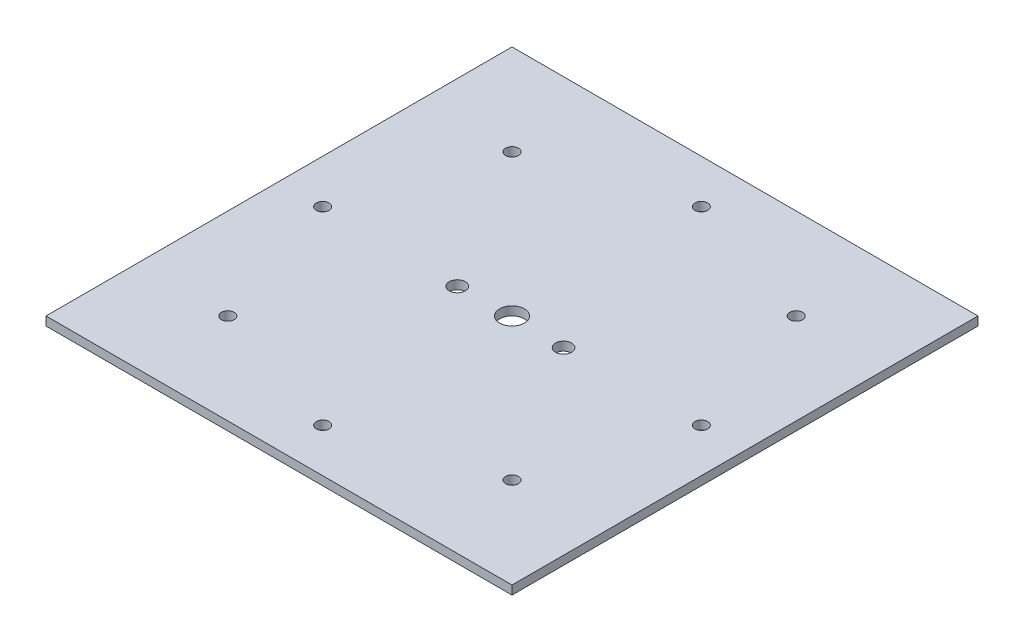
SolidWorks part; units mm, degrees
ref_plane "Front Plane" through (0, 0, 0) normal (0, 0, 1) x (1, 0, 0)
ref_plane "Top Plane" through (0, 0, 0) normal (0, 1, 0) x (1, 0, 0)
ref_plane "Right Plane" through (0, 0, 0) normal (1, 0, 0) x (0, 0, -1)
sketch "Sketch1" plane through (0, 0, 0) normal (0, 1, 0) x (1, 0, 0)
  line L0 (0, 80) -> (0, -80) construction
  line L1 (-80, 80) -> (80, 80)
  line L2 (-80, 80) -> (-80, -80)
  line L3 (-80, -80) -> (80, -80)
  line L4 (80, 80) -> (80, -80)
  line L5 (-80, 80) -> (80, -80) construction
  line L6 (-80, -80) -> (80, 80) construction
  circle A0 centre (0, 0) radius 69 construction
  circle A2 centre (48.7904, 48.7904) radius 2.2
  circle A4 centre (48.7904, -48.7904) radius 2.2
  circle A6 centre (-48.7904, -48.7904) radius 2.2
  circle A8 centre (-48.7904, 48.7904) radius 2.2
  circle A9 centre (0, 0) radius 4.25
  circle A10 centre (18.2724, -0.5716) radius 2.75
  circle A11 centre (-18.2276, -0.5716) radius 2.75
  circle A12 centre (0, 0) radius 65 construction
  circle A13 centre (0, 65) radius 2.2
  circle A14 centre (65, 0) radius 2.2
  circle A15 centre (0, -65) radius 2.2
  circle A16 centre (-65, 0) radius 2.2
  point P0 (0, 0)
  point P13 (0, 0)
  point P16 (0, 0)
  point P19 (0, 0)
  point P22 (0, 0)
  point P25 (0, 0)
  point P28 (0, 0)
  point P31 (0, 0)
  point P34 (0, 0)
  point P43 (0, 0)
  dimension "D3" = 8
  dimension "D4" = 4
  dimension "D1" = 160
  dimension "D2" = 160
extrude "Boss-Extrude1" add sketch "Sketch1" along normal blind 3
